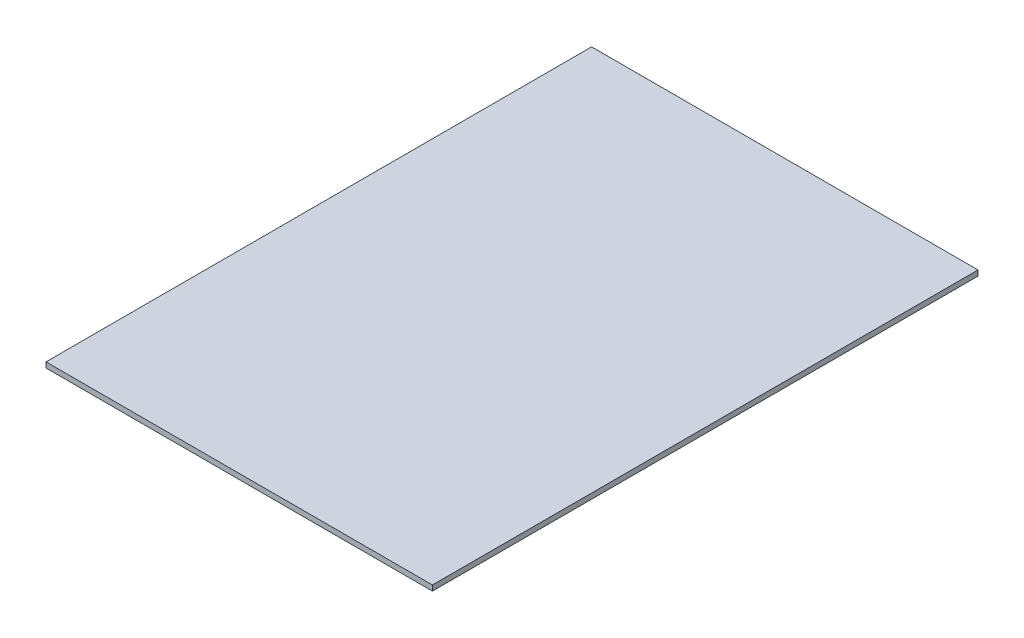
SolidWorks part; units mm, degrees
ref_plane "Alzado" through (0, 0, 0) normal (0, 0, 1) x (1, 0, 0)
ref_plane "Planta" through (0, 0, 0) normal (0, 1, 0) x (1, 0, 0)
ref_plane "Vista lateral" through (0, 0, 0) normal (1, 0, 0) x (0, 0, -1)
sketch "Croquis1" plane through (0, 0, 0) normal (0, 1, 0) x (1, 0, 0)
  line L1 (108, 155) -> (-108, 155)
  line L2 (108, 155) -> (108, -155)
  line L3 (108, -155) -> (-108, -155)
  line L4 (-108, 155) -> (-108, -155)
  line L5 (108, 155) -> (-108, -155) construction
  line L6 (108, -155) -> (-108, 155) construction
  point P0 (0, 0)
  dimension "D1" = 216
  dimension "D2" = 310
extrude "Saliente-Extruir1" add sketch "Croquis1" along normal blind 3
sketch "Croquis2" plane through (0, 3, 0) normal (0, 1, 0) x (1, 0, 0)
  line L5 (108, -155) -> (108, 155) construction
  line L6 (-108, 155) -> (108, 155)
  line L12 (-108, 155) -> (-108, 152.5)
  line L13 (-108, 152.5) -> (108, 152.5)
  line L18 (108, 155) -> (108, 152.5)
  line L19 (-108, 155) -> (108, 152.5) construction
  line L20 (-108, 152.5) -> (108, 155) construction
  line L26 (-108, -155) -> (108, -155)
  line L27 (-108, -155) -> (-108, -152.5)
  line L28 (-108, -152.5) -> (108, -152.5)
  line L29 (108, -155) -> (108, -152.5)
  line L30 (-108, -155) -> (108, -152.5) construction
  line L31 (-108, -152.5) -> (108, -155) construction
  point P4 (0, 153.75)
  point P11 (0, -153.75)
  dimension "D1" = 2.5
extrude "Cortar-Extruir1" cut sketch "Croquis2" against normal blind 4
equation "\"venesta\"= 4'grosor de la venesta"
equation "\"policarbonato\"= 4'grosor del policarbonato"
equation "\"carton_trupan\"= 3'grosor del carton trupan caso laser"
equation "\"ancho_tot\"= 310'ancho tot sin llantas"
equation "\"largo_tot\"= 400'largo tot sin camera"
equation "\"alto_estimado\"= 300'alto estimado sin lidar"
equation "\"altoparaqpaselabotella\"= 75'alto estimado para que encaje la botella"
equation "\"alturaruedaloca\"= 22"
equation "\"anchoruedaloca\"= 35"
equation "\"anchopiso1motorybaterias\"= 150"
equation "\"dist-pisorampa\"= 5"
equation "\"anchoultimopiso\"= 170"
equation "\"paredtrasera\"= 100"
equation "\"agarradorcanasta\"= 275'recolector"
equation "\"alturapiso1y2\"= 80"
equation "\"alturapiso2y3\"= 80"
equation "\"D2@Croquis1\"=\"ancho_tot\""
equation "\"D1@Saliente-Extruir1\"=\"carton_trupan\""
equation "\"TOLERANCIA\"= 0.05"
equation "\"GROSOR_PARED_IMPRESION\"= 2.5"
equation "\"D1@Croquis2\"=\"GROSOR_PARED_IMPRESION\""
